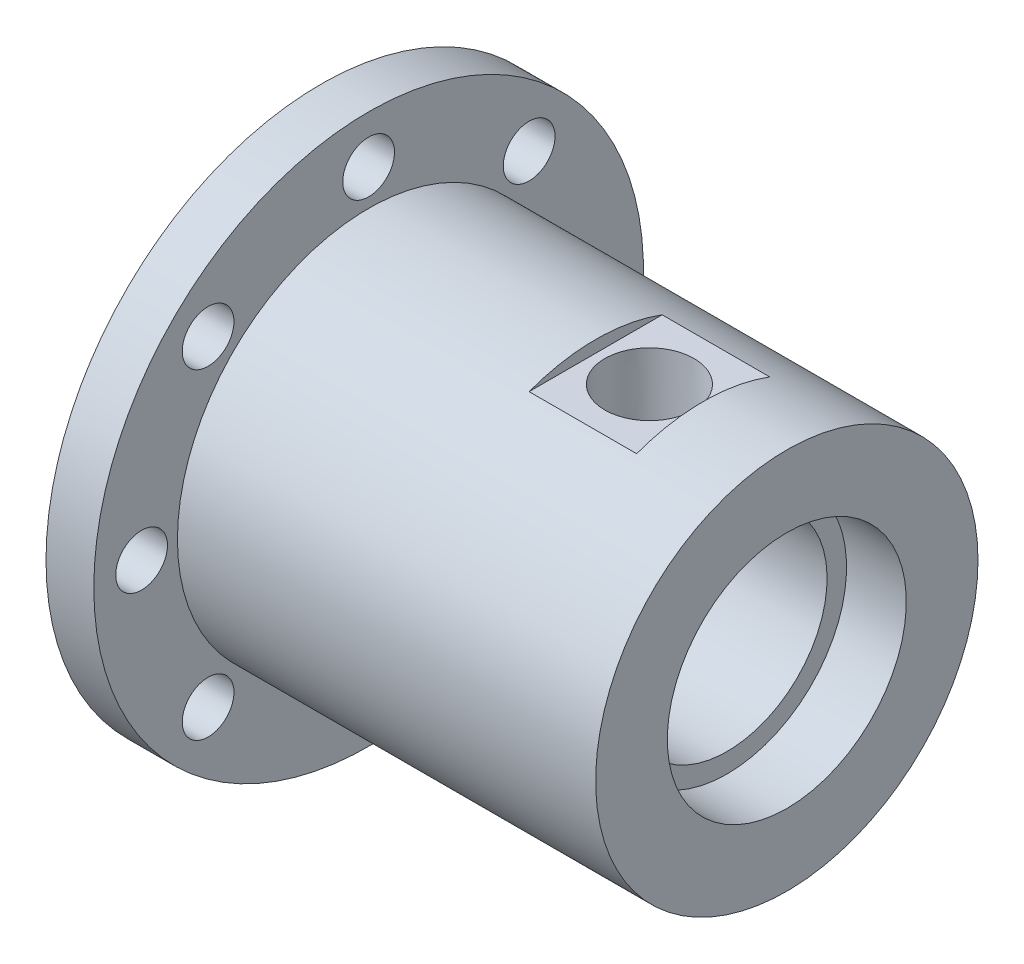
SolidWorks part; units mm, degrees
ref_plane "Front Plane" through (0, 0, 0) normal (0, 0, 1) x (1, 0, 0)
ref_plane "Top Plane" through (0, 0, 0) normal (0, 1, 0) x (1, 0, 0)
ref_plane "Right Plane" through (0, 0, 0) normal (1, 0, 0) x (0, 0, -1)
sketch "Sketch1" plane through (0, 0, 0) normal (0, 0, 1) x (1, 0, 0)
  line L0 (-30.6578, 10.6299) -> (-30.6578, 11.9507)
  line L1 (-49.53, 0) -> (-49.53, 12.7)
  line L2 (-49.53, 12.7) -> (-34.29, 12.7)
  line L3 (-34.29, 12.7) -> (-34.29, 10.6299)
  line L4 (-34.29, 10.6299) -> (-33.02, 10.6299)
  line L5 (-28.8798, 10.6299) -> (-28.8798, 11.9507)
  line L6 (-28.8798, 11.9507) -> (-26.5176, 11.9507)
  line L7 (-26.5176, 11.9507) -> (-26.5176, 10.6299)
  line L11 (-6.35, 10.6299) -> (-6.35, 12.7)
  line L12 (-6.35, 12.7) -> (0, 12.7)
  line L16 (0, 0) -> (-49.53, 0)
  line L17 (-30.6578, 11.9507) -> (-33.02, 11.9507)
  line L18 (-33.02, 11.9507) -> (-33.02, 10.6299)
  line L19 (-30.6578, 10.6299) -> (-28.8798, 10.6299)
  line L20 (0, 0) -> (0, 12.7)
  line L21 (-26.5176, 10.6299) -> (-6.35, 10.6299)
  dimension "D1" = 6.35
  dimension "D2" = 2.3622
  dimension "D3" = 1.3208
  dimension "D9" = 1.27
  dimension "D10" = 12.7
  dimension "D11" = 15.24
  dimension "D7" = 12.7
  dimension "D4" = 11.9507
  dimension "D12" = 1.778
  dimension "D5" = 49.53
sketch "Sketch2" plane through (0, 0, 0) normal (1, 0, 0) x (0, 0, -1)
  circle A0 centre (0, 0) radius 20.32
  dimension "D1" = 40.64
extrude "Boss-Extrude1" add sketch "Sketch2" against normal blind 49.53
revolve "Cut-Revolve1" cut sketch "Sketch1" angle 360 about L16
sketch "Sketch3" plane through (-49.53, 0, 0) normal (-1, 0, 0) x (0, 0, 1)
  circle A0 centre (0, 0) radius 19.05
  circle A1 centre (0, 0) radius 29.21
  dimension "D1" = 58.42
extrude "Boss-Extrude2" add sketch "Sketch3" against normal blind 5.08
sketch "Sketch4" plane through (-44.45, 0, 0) normal (1, 0, 0) x (0, 0, -1)
  circle A2 centre (0, 0) radius 24.13
  circle A3 centre (0, 0) radius 24.13 construction
  point P0 (0, 24.13)
  point P12 (0, 0)
  point P15 (0, 0)
  point P78 (17.0625, 17.0625)
  point P79 (24.13, 0)
  point P80 (17.0625, -17.0625)
  point P81 (0, -24.13)
  point P82 (-17.0625, -17.0625)
  point P83 (-24.13, 0)
  point P84 (-17.0625, 17.0625)
  dimension "D1" = 5.08
  dimension "D2" = 8
hole_wizard "M5 Clearance Hole1" positions "Sketch4" profile "Sketch5" hole size "M5" standard "ISO" end condition up to next
sketch "Sketch5" plane through (-44.45, 24.13, 0) normal (0, 1, 0) x (0, 0, -1)
  line L0 (0, 0) -> (0, 5.08)
  line L1 (0, 5.08) -> (2.75, 5.08)
  line L2 (2.75, 5.08) -> (2.75, 0)
  line L5 (2.75, 0) -> (0, 0)
  line L11 (0, -6.35) -> (0, 107.95) construction
  dimension "Thru Hole Dia." = 5.5
  dimension "Thru Hole Depth" = 5.08
ref_plane "Plane1" through (0, 20.32, 0) normal (0, 1, 0) x (1, 0, 0)
sketch "Sketch6" plane through (0, 20.32, 0) normal (0, 1, 0) x (1, 0, 0)
  line L0 (0, 0) -> (-8.89, 0) construction
  line L1 (-20.32, 12.7) -> (-8.89, 12.7)
  line L2 (-20.32, 12.7) -> (-20.32, -12.7)
  line L3 (-20.32, -12.7) -> (-8.89, -12.7)
  line L4 (-8.89, 12.7) -> (-8.89, -12.7)
  line L5 (0, -20.32) -> (0, 20.32) construction
  dimension "D1" = 8.89
  dimension "D2" = 11.43
  dimension "D3" = 25.4
extrude "Cut-Extrude1" cut sketch "Sketch6" against normal blind 1.27
sketch "Sketch7" plane through (0, 19.05, 0) normal (0, 1, 0) x (1, 0, 0)
  line L0 (-20.32, 7.0711) -> (-8.89, -7.0711) construction
  line L1 (-8.89, 7.0711) -> (-20.32, -7.0711) construction
  point P8 (-14.605, 0)
hole_wizard "1/8 NPT Tapped Hole1" positions "Sketch7" profile "Sketch8" size "1/8" standard "ANSI Inch" end condition up to next
sketch "Sketch8" plane through (-14.605, 19.05, 0) normal (1, 0, 0) x (0, 0, 1)
  line L0 (0, 0) -> (0, 8.4201)
  line L1 (0, 8.4201) -> (4.2164, 8.4201)
  line L2 (-4.5374, 6.858) -> (-4.7427, 0) construction
  line L3 (4.2164, 8.4201) -> (4.2164, 6.858)
  line L4 (4.2164, 6.858) -> (4.5374, 6.858)
  line L5 (4.5374, 6.858) -> (4.7427, 0)
  line L7 (4.7427, 0) -> (0, 0)
  line L8 (0, -6.35) -> (0, 107.95) construction
  line L11 (-4.2164, 6.858) -> (-4.5374, 6.858) construction
  dimension "Thru Tap Drill Dia." = 8.4328
  dimension "Thru Tap Drill Depth" = 8.4201
  dimension "Thread Dia." = 9.4855
  dimension "Thread Angle" = 3.43
  dimension "Thread Depth" = 6.858
cosmetic thread "Hole Thread1" parameters "D1"=6.858, "D2"=10.2827
sketch "Sketch9" plane through (-49.53, 0, 0) normal (-1, 0, 0) x (0, 0, 1)
  circle A0 centre (0, 0) radius 16.7132
  circle A1 centre (0, 0) radius 14.1478
  dimension "D1" = 33.4264
  dimension "D2" = 2.5654
extrude "Cut-Extrude2" cut sketch "Sketch9" against normal blind 1.27
equation "\"lip_seal_width\"= 0.25in"
equation "\"D1@Sketch1\"=\"lip_seal_width\""
equation "\"Cavity_Depth\" = 0.031in"
equation "\"Cavity_Width\" = 0.031in"
equation "\"Tooth_Width\" = .01in"
equation "\"Shaft_Seal_OD\"= 17mm'diameter at seal area"
equation "\"Shaft_clearance\"= .002in"
equation "\"O-Ring_ID\"= .801in"
equation "\"O-Ring_CS\"= .070in"
equation "\"Shaft_OD\"= .5in"
equation "\"post_laby_len\"= 1.25in"
equation "\"lip_seal_OD\"= 1in"
equation "\"D7@Sketch1\"=\"lip_seal_OD\"/2"
equation "\"Casing_OD\"= 1.6in"
equation "\"D1@Sketch2\"=\"Casing_OD\""
equation "\"D4@Sketch1\"=\"O-Ring_ID\"/2 + \"O-Ring_CS\""
equation "\"Flange_OD\"=2.3in"
equation "\"D1@Sketch3\"=\"Flange_OD\""
equation "\"D1@Sketch6\"=\"lip_seal_width\"+.1"
equation "\"total_len\"= 1.95"
equation "\"D5@Sketch1\"=\"total_len\""
equation "\"D1@Boss-Extrude1\"=\"total_len\""
